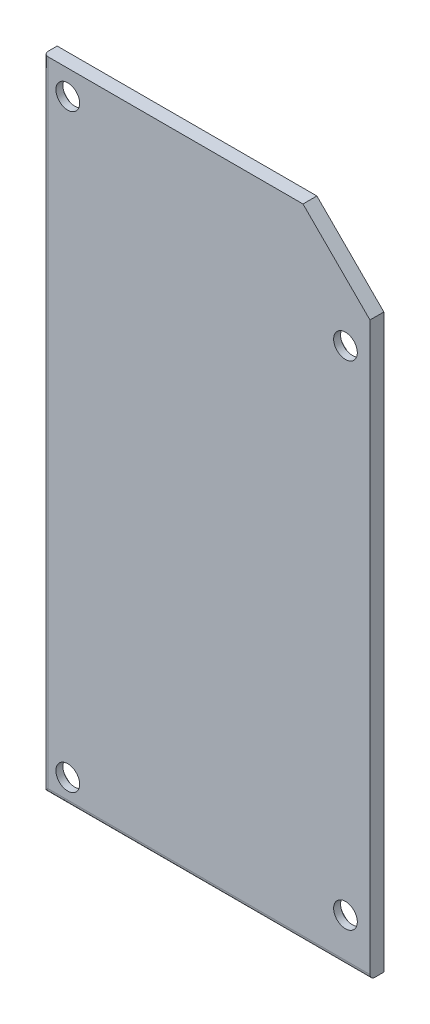
SolidWorks part; units mm, degrees
ref_plane "Front Plane" through (0, 0, 0) normal (0, 0, 1) x (1, 0, 0)
ref_plane "Top Plane" through (0, 0, 0) normal (0, 1, 0) x (1, 0, 0)
ref_plane "Right Plane" through (0, 0, 0) normal (1, 0, 0) x (0, 0, -1)
sketch "Sketch1" plane through (0, 0, 0) normal (0, 0, 1) x (1, 0, 0)
  line L0 (31.8, 78.2) -> (40, 70)
  line L1 (0, 0) -> (40, 0)
  line L3 (0, 78.2) -> (31.8, 78.2)
  line L4 (40, 0) -> (40, 70)
  line L5 (0, 0) -> (0, 3)
  line L6 (6, 75.2) -> (30.5574, 75.2)
  line L7 (35.2, 3) -> (6, 3)
  line L8 (37, 8.4) -> (37, 62.7574)
  line L10 (-74.4457, 75.2) -> (30.5574, 75.2) construction
  line L11 (1.2019, 3) -> (-74.4457, 75.2) construction
  line L12 (30.5574, 75.2) -> (37, 68.7574)
  line L13 (30.5574, 75.2) -> (37, 68.7574) construction
  line L14 (1.2019, 3) -> (37, 3) construction
  line L15 (37, 3) -> (37, 68.7574) construction
  line L16 (0, 78.2) -> (0, 75.2)
  line L17 (-81.934, 78.2) -> (31.8, 78.2) construction
  line L18 (40, 0) -> (40, 70) construction
  line L19 (0, 0) -> (-81.934, 78.2) construction
  arc A0 (37, 68.7574) -> (37, 62.7574) centre (37, 65.7574) ccw
  circle A1 centre (37, 65.7574) radius 1.025
  arc A2 (37, 8.4) -> (35.2, 3) centre (37, 5.4) ccw
  circle A3 centre (37, 5.4) radius 1.025
  arc A4 (6, 3) -> (0, 3) centre (3, 3) ccw
  circle A5 centre (3, 3) radius 1.025
  arc A6 (0, 75.2) -> (6, 75.2) centre (3, 75.2) ccw
  circle A7 centre (3, 75.2) radius 1.025
  dimension "D6" = 6
  dimension "D7" = 2.05
  dimension "D1" = 40
  dimension "D2" = 135
  dimension "D3" = 3
  dimension "D4" = 70
  dimension "D5" = 3
extrude "Boss-Extrude1" add sketch "Sketch1" along normal blind 28
sketch "Sketch2" plane through (0, 78.2, 0) normal (0, 1, 0) x (1, 0, 0)
  line L0 (31.8, -14) -> (-12.3888, -14) construction
  line L1 (31.8, -28) -> (31.8, 0) construction
  circle A0 centre (16.8, -14) radius 13
  dimension "D1" = 26
  dimension "D2" = 15
extrude "Cut-Extrude1" cut sketch "Sketch2" against normal blind 0.6
sketch "Sketch3" plane through (0, 77.6, 0) normal (0, 1, 0) x (1, 0, 0)
  line L0 (16.8, -14) -> (48.7255, -14) construction
  line L2 (26.8399, -12.9) -> (28.0399, -12.9)
  line L4 (26.8399, -15.1) -> (28.0399, -15.1)
  line L5 (28.0399, -12.9) -> (28.0399, -15.1)
  arc A0 (26.8399, -12.9) -> (26.8399, -15.1) centre (16.8, -14) ccw
  dimension "D1" = 20.2
  dimension "D2" = 1.2
  dimension "D3" = 2.2
extrude "Cut-Extrude2" cut sketch "Sketch3" against normal up to next
fillet "Fillet1" radius 0.4 4 edges at (6.7, 77.6, 14) (27.4399, 77.6, 15.1) (28.0399, 77.6, 14) (27.4399, 77.6, 12.9)
sketch "Sketch14" plane through (40, 0, 0) normal (1, 0, 0) x (0, 0, -1)
  line L0 (-14, 70) -> (-14, 0) construction
  line L1 (-28, 70) -> (0, 70) construction
  line L3 (-14, 28) -> (13.9962, 28) construction
  line L4 (-19.9, 47.7) -> (-5.1, 47.7) construction
  line L5 (-15.9, 52.4) -> (-8.1, 52.4)
  line L6 (-19.9, 48.4) -> (-19.9, 47)
  line L7 (-15.9, 43) -> (-8.1, 43)
  line L8 (-8.1, 52.4) -> (-8.1, 43)
  line L9 (-19.2, 57.65) -> (4.7334, 57.65) construction
  line L10 (-19.2, 60.4) -> (-8.8, 60.4)
  line L11 (-19.2, 60.4) -> (-19.2, 54.9)
  line L12 (-19.2, 54.9) -> (-8.8, 54.9)
  line L13 (-8.8, 60.4) -> (-8.8, 54.9)
  line L14 (-7.75, 47.7) -> (3.1305, 47.7) construction
  line L15 (-28, 0) -> (0, 0) construction
  line L17 (-23, 12) -> (-5, 12)
  line L18 (-23, 12) -> (-23, 3)
  line L19 (-23, 3) -> (-5, 3)
  line L20 (-5, 12) -> (-5, 3)
  circle A0 centre (-14, 28) radius 8
  circle A1 centre (-14, 16.9) radius 1.6
  circle A2 centre (-14, 39.1) radius 1.6
  circle A3 centre (-6.3, 47.7) radius 1.45
  circle A4 centre (-21.7, 47.7) radius 1.45
  arc A5 (-15.9, 52.4) -> (-19.9, 48.4) centre (-15.9, 48.4) ccw
  arc A6 (-19.9, 47) -> (-15.9, 43) centre (-15.9, 47) ccw
  circle A7 centre (-22.5, 57.65) radius 1.45
  circle A8 centre (-5.5, 57.65) radius 1.45
  point P27 (-19.9, 52.4)
  point P40 (-19.9, 43)
  dimension "D1" = 16
  dimension "D2" = 3.2
  dimension "D7" = 2.9
  dimension "D9" = 4
  dimension "D13" = 2.9
  dimension "D3" = 22.2
  dimension "D4" = 28
  dimension "D5" = 9.4
  dimension "D6" = 11.8
  dimension "D8" = 15.4
  dimension "D10" = 15
  dimension "D11" = 10.4
  dimension "D12" = 5.5
  dimension "D14" = 17
  dimension "D15" = 2.5
  dimension "D16" = 18
  dimension "D17" = 3
  dimension "D18" = 9
extrude "Cut-Extrude9" cut sketch "Sketch14" against normal through all
fillet "Fillet2" radius 5 8 edges at (35.2, 3, 25.5) (35.2, 3, 2.5) (37, 68.7574, 14) (6, 3, 2.5) (6, 3, 25.5) (37, 8.4, 25.5) (37, 8.4, 2.5) (6, 75.2, 14)
ref_plane "Plane1" through (0, 0, 14) normal (0, 0, 1) x (1, 0, 0)
sketch "Sketch16" plane through (0, 0, 14) normal (0, 0, 1) x (1, 0, 0)
  line L0 (1.975, 3) -> (4.025, 3)
  arc A0 (1.975, 3) -> (4.025, 3) centre (3, 3) ccw
  circle A1 centre (3, 3) radius 1.025 construction
extrude "Boss-Extrude2" add sketch "Sketch16" along normal mid plane 18
sketch "Sketch17" plane through (0, 3, 0) normal (0, 1, 0) x (1, 0, 0)
  line L0 (-22, -14) -> (22, -14) construction
  line L2 (10, -15.7) -> (10, -12.3) construction
  line L3 (4, -15.7) -> (4, -12.3)
  line L4 (16, -15.7) -> (16, -12.3)
  line L5 (-1.8935, -14) -> (39.7453, -14) construction
  arc A1 (4, -15.7) -> (16, -15.7) centre (10, -15.7) ccw
  arc A2 (16, -12.3) -> (4, -12.3) centre (10, -12.3) ccw
  point P8 (10, -14)
  dimension "D3" = 6
  dimension "D4" = 3.4
extrude "Boss-Extrude3" add sketch "Sketch17" along normal blind 1.76
sketch "Sketch18" plane through (0, 4.76, 0) normal (0, 1, 0) x (1, 0, 0)
  line L0 (-1.8826, -14) -> (40.0349, -14) construction
  line L1 (-22, -14) -> (22, -14) construction
  line L2 (10, -15.7) -> (10, -12.3) construction
  line L3 (6.43, -15.7) -> (6.43, -12.3)
  line L4 (13.57, -15.7) -> (13.57, -12.3)
  arc A1 (6.43, -15.7) -> (13.57, -15.7) centre (10, -15.7) ccw
  arc A2 (13.57, -12.3) -> (6.43, -12.3) centre (10, -12.3) ccw
  point P9 (10, -14)
  dimension "D2" = 3.57
  dimension "D3" = 3.4
extrude "Cut-Extrude10" cut sketch "Sketch18" against normal up to next
fillet "Fillet3" radius 5 4 edges at (4, 3, 14) (10, 3, 6.3) (16, 3, 14) (10, 3, 21.7)
sketch "Sketch19" plane through (0, 3, 0) normal (0, 1, 0) x (1, 0, 0)
  line L0 (-1.4647, -14) -> (47.0035, -14) construction
  line L1 (-22, -14) -> (22, -14) construction
  line L2 (29.4343, 0) -> (9.245, 0) construction
  line L3 (40, -22) -> (40, -6) construction
  line L4 (29.4343, -5) -> (29.4343, 0) construction
  circle A0 centre (24, -3.25) radius 1.025
  circle A1 centre (24, -24.75) radius 1.025
  dimension "D1" = 2.05
  dimension "D3" = 3.25
  dimension "D4" = 16
  dimension "D5" = 5.4343
  dimension "D2" = 21.5
extrude "Cut-Extrude11" cut sketch "Sketch19" against normal up to next
fillet "Fillet4" radius 0.6 5 edges at (37, 12, 14) (40, 7.5, 5) (40, 3, 14) (40, 7.5, 23) (40, 12, 14)
sketch "Sketch20" plane through (0, 0, 0) normal (-1, 0, 0) x (0, 0, 1)
  line L0 (14, 87.38) -> (14, -6.6146) construction
  line L1 (14, -22) -> (14, 22) construction
  line L2 (5, 3) -> (5, 109.2462) construction
  line L3 (23, 3) -> (23, 109.2462) construction
  line L4 (28, 75.2) -> (0, 75.2) construction
  line L5 (23, 75.2) -> (5, 75.2)
  line L6 (23, 75.2) -> (23, 72.2)
  line L7 (23, 72.2) -> (5, 72.2)
  line L8 (5, 75.2) -> (5, 72.2)
  line L9 (0, 72.2) -> (28, 72.2) construction
extrude "Cut-Extrude12" cut sketch "Sketch20" against normal up to next
sketch "Sketch21" plane through (0, 0, 14) normal (0, 0, 1) x (1, 0, 0)
  line L0 (1.975, 75.2) -> (4.025, 75.2)
  arc A0 (4.025, 75.2) -> (1.975, 75.2) centre (3, 75.2) ccw
extrude "Boss-Extrude4" add sketch "Sketch21" along normal mid plane 18
fillet "Fillet5" radius 2.5 1 edges at (37, 62.7574, 14)
sketch "Sketch22" plane through (0, 0, 28) normal (0, 0, 1) x (1, 0, 0)
  line L0 (0, 78.2) -> (31.8, 78.2)
  line L1 (31.8, 78.2) -> (40, 70)
  line L2 (40, 70) -> (40, 0)
  line L3 (40, 0) -> (0, 0)
  line L4 (0, 0) -> (0, 78.2)
  line L5 (1.975, 75.2) -> (4.025, 75.2) construction
  circle A0 centre (3, 75.2) radius 1.45
  circle A1 centre (37, 65.7574) radius 1.45
  circle A2 centre (37, 5.4) radius 1.45
  circle A3 centre (3, 3) radius 1.45
  dimension "D1" = 2.9
extrude "Boss-Extrude5" add sketch "Sketch22" along normal blind 1.7
sketch "Sketch23" plane through (0, 0, 28) normal (0, 0, -1) x (-1, 0, 0)
  line L1 (-46.1974, 80.9815) -> (11.5404, 80.9815)
  line L2 (-46.1974, 80.9815) -> (-46.1974, -7.2626)
  line L3 (-46.1974, -7.2626) -> (11.5404, -7.2626)
  line L4 (11.5404, 80.9815) -> (11.5404, -7.2626)
extrude "Cut-Extrude13" cut sketch "Sketch23" along normal through all
sketch "Sketch24" plane through (0, 0, 28) normal (0, 0, 1) x (1, 0, 0)
  circle A0 centre (3, 75.2) radius 2.6
  circle A1 centre (37, 65.7574) radius 2.6
  circle A2 centre (3, 3) radius 2.6
  circle A3 centre (37, 5.4) radius 2.6
  dimension "D1" = 5.2
extrude "Cut-Extrude14" cut sketch "Sketch24" along normal blind 0.85
fillet "Fillet7" radius 0.6 2 edges at (20, 0, 29.7) (0, 39.1, 29.7)
